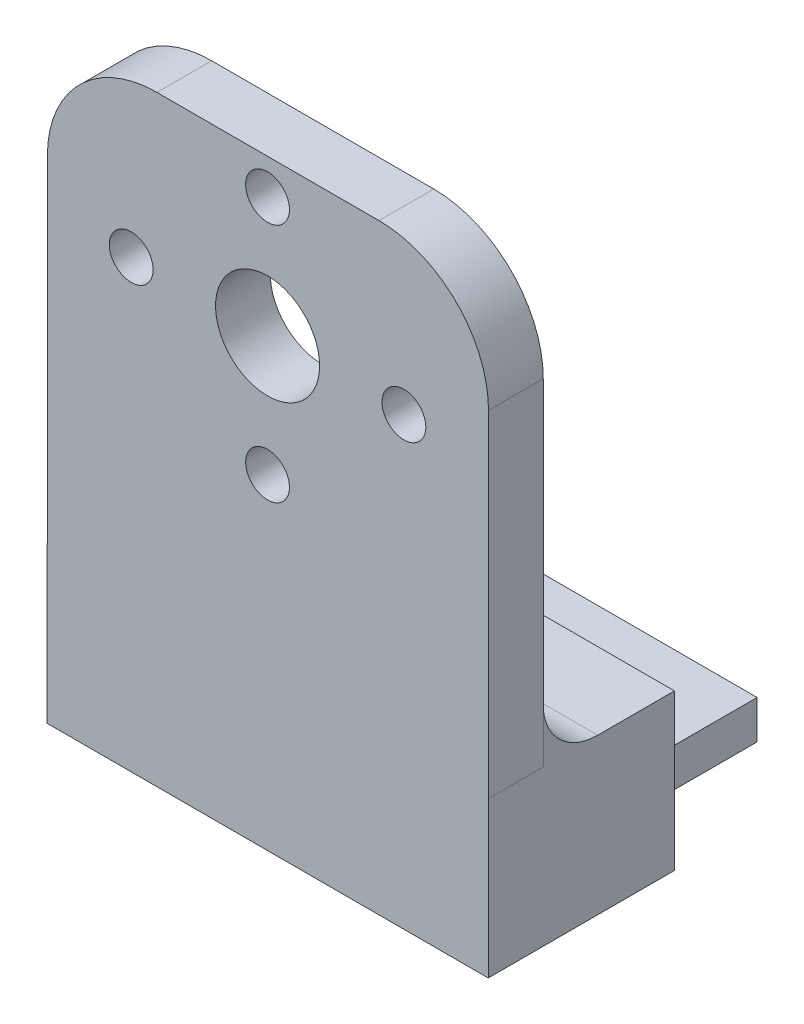
SolidWorks part; units mm, degrees
ref_plane "Front Plane" through (0, 0, 0) normal (0, 0, 1) x (1, 0, 0)
ref_plane "Top Plane" through (0, 0, 0) normal (0, 1, 0) x (1, 0, 0)
ref_plane "Right Plane" through (0, 0, 0) normal (1, 0, 0) x (0, 0, -1)
sketch "Sketch1" plane through (0, 0, 0) normal (0, 1, 0) x (1, 0, 0)
  line L1 (20.15, 8.5) -> (-20.15, 8.5)
  line L2 (20.15, 8.5) -> (20.15, -8.5)
  line L3 (20.15, -8.5) -> (-20.15, -8.5)
  line L4 (-20.15, 8.5) -> (-20.15, -8.5)
  line L5 (20.15, 8.5) -> (-20.15, -8.5) construction
  line L6 (20.15, -8.5) -> (-20.15, 8.5) construction
  point P0 (0, 0)
  dimension "D1" = 40.3
extrude "Boss-Extrude1" add sketch "Sketch1" along normal blind 11 and the other way blind 3.2
sketch "Sketch2" plane through (0, 0, -8.5) normal (0, 0, -1) x (-1, 0, 0)
  line L0 (-20.15, -3.2) -> (20.15, -3.2) construction
  line L1 (-18, 4.5571) -> (18, 4.5571)
  line L2 (-18, 4.5571) -> (-18, 1.044)
  line L3 (-18, 1.044) -> (18, 1.044)
  line L4 (18, 4.5571) -> (18, 1.044)
  line L5 (-20.15, 11) -> (-20.15, -3.2) construction
  line L6 (20.15, 11) -> (20.15, -3.2) construction
  line L7 (0, 4.5571) -> (0, 11)
  line L8 (-20.15, 11) -> (20.15, 11) construction
  point P0 (0, 8)
  point P7 (0, -3.2)
  dimension "D1" = 2.15
  dimension "D2" = 2.15
extrude "Boss-Extrude2" add sketch "Sketch2" along normal blind 9.7 contours L4 L1 L2 L3 region at (0, 2.8005, -8.5)
sketch "Sketch3" plane through (0, 11, 0) normal (0, 1, 0) x (1, 0, 0)
  line L1 (20.1732, -3.5) -> (-20.1016, -3.5)
  line L2 (20.1732, -3.5) -> (20.1732, -8.5)
  line L3 (20.1732, -8.5) -> (-20.1016, -8.5)
  line L4 (-20.1016, -3.5) -> (-20.1016, -8.5)
extrude "Boss-Extrude3" add sketch "Sketch3" along normal blind 40.7
sketch "Sketch4" plane through (0, 0, 8.5) normal (0, 0, 1) x (1, 0, 0)
  line L0 (0, -3.2) -> (0, 37.5)
  line L1 (-20.15, -3.2) -> (20.15, -3.2) construction
  line L2 (-4.75, 37.5) -> (-20.15, 37.5)
  line L7 (0, 37.5) -> (0, 25.3)
  line L8 (-20.15, 11) -> (-20.15, -3.2) construction
  line L9 (4.75, 37.5) -> (20.15, 37.5)
  line L10 (20.15, 11) -> (20.15, -3.2) construction
  circle A0 centre (0, 37.5) radius 4.75
  circle A1 centre (-12.45, 37.5) radius 2
  circle A2 centre (12.45, 37.5) radius 2
  circle A3 centre (0, 48.475) radius 2
  circle A4 centre (0, 26.525) radius 2
  point P24 (0, 50.7)
extrude "Cut-Extrude1" cut sketch "Sketch4" against normal blind 5 contours A0 | A4 L7 | A4 L7 | A1 | A2 | A3 region at (-0.8488, 26.525, 8.5) region at (-3.2638, 34.2362, 8.5) region at (0.8488, 26.525, 8.5)
fillet "Fillet1" radius 10 2 edges at (-20.1016, 51.7, 6) (20.1732, 51.7, 6)
fillet "Fillet2" radius 5 1 edges at (0.0242, 11, 3.5)
